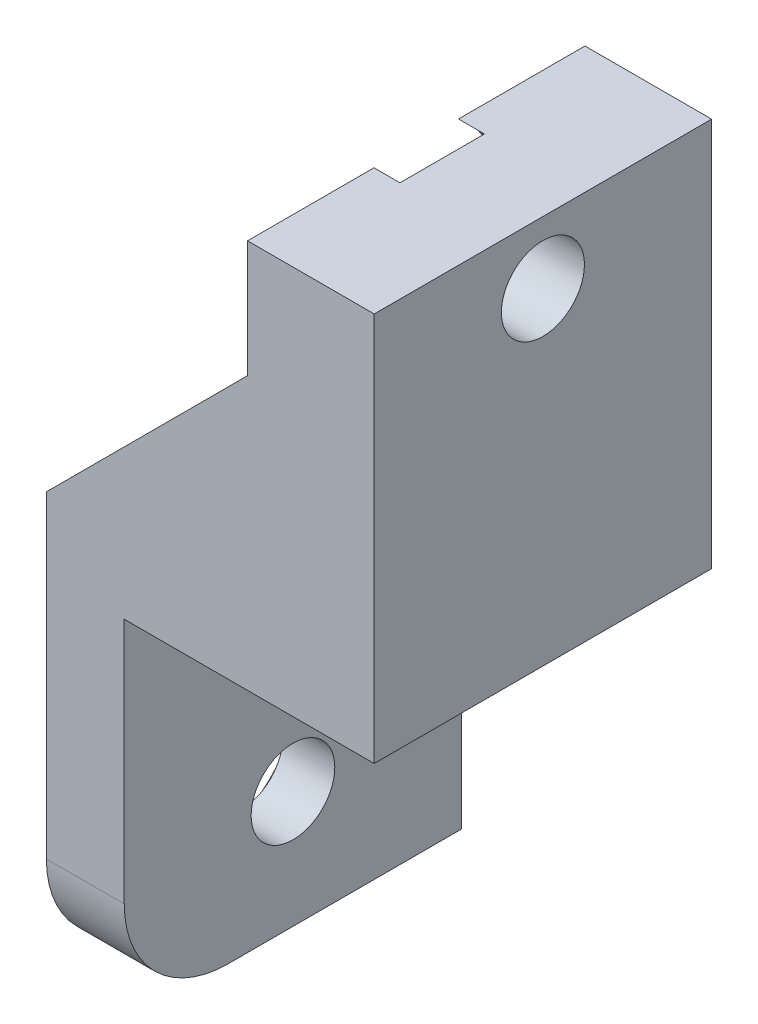
SolidWorks part; units mm, degrees
ref_plane "Front Plane" through (0, 0, 0) normal (0, 0, 1) x (1, 0, 0)
ref_plane "Top Plane" through (0, 0, 0) normal (0, 1, 0) x (1, 0, 0)
ref_plane "Right Plane" through (0, 0, 0) normal (1, 0, 0) x (0, 0, -1)
sketch "Sketch1" plane through (0, 0, 98.1716) normal (0, 0, 1) x (1, 0, 0)
  line L0 (32.7844, 63.2635) -> (26.5844, 63.2635) construction
  line L1 (30.3344, 78.2635) -> (35.2144, 78.2635)
  line L2 (30.3344, 78.2635) -> (30.3344, 63.7635)
  line L4 (35.2144, 78.2635) -> (35.2144, 65.8635)
  line L5 (22.5844, 49.7635) -> (25.5844, 49.7635)
  line L6 (22.5844, 49.7635) -> (22.5844, 63.2635)
  line L8 (25.5844, 49.7635) -> (25.5844, 63.2635)
  line L21 (30.3344, 63.7635) -> (22.5844, 63.7635)
  line L22 (22.5844, 63.7635) -> (22.5844, 63.2635)
  line L25 (25.5844, 63.2635) -> (35.2144, 63.2635)
  line L26 (35.2144, 63.2635) -> (35.2144, 65.8635)
  dimension "D1" = 14.5
  dimension "D2" = 3
  dimension "D3" = 0
  dimension "D4" = 4.88
  dimension "D6" = 0
  dimension "D7" = 14
  dimension "D8" = 0.5
  dimension "D9" = 4.75
extrude "Boss-Extrude1" add sketch "Sketch1" against normal blind 13
sketch "Sketch2" plane through (35.2144, 0, 0) normal (1, 0, 0) x (0, 0, -1)
  line L0 (-85.1716, 49.7635) -> (-98.1716, 49.7635) construction
  circle A0 centre (-91.6716, 75.8635) radius 1.6
  circle A1 centre (-91.6716, 54.2635) radius 1.6115
  dimension "D1" = 4.5
extrude "Cut-Extrude1" cut sketch "Sketch2" against normal blind 30 and the other way blind 10
sketch "Sketch3" plane through (22.5844, 0, 0) normal (-1, 0, 0) x (0, 0, 1)
  circle A0 centre (91.6716, 54.2635) radius 3
  dimension "D1" = 6
extrude "Cut-Extrude2" cut sketch "Sketch3" against normal blind 1
sketch "Sketch4" plane through (30.3344, 0, 0) normal (-1, 0, 0) x (0, 0, 1)
  circle A0 centre (91.6716, 75.8635) radius 2.9
  dimension "D1" = 5.8
extrude "Cut-Extrude3" cut sketch "Sketch4" against normal blind 1
chamfer "Chamfer1" distance 10 angle 45 1 edges at (30.3344, 63.7635, 91.6716)
fillet "Fillet1" radius 4 1 edges at (24.0844, 49.7635, 98.1716)
